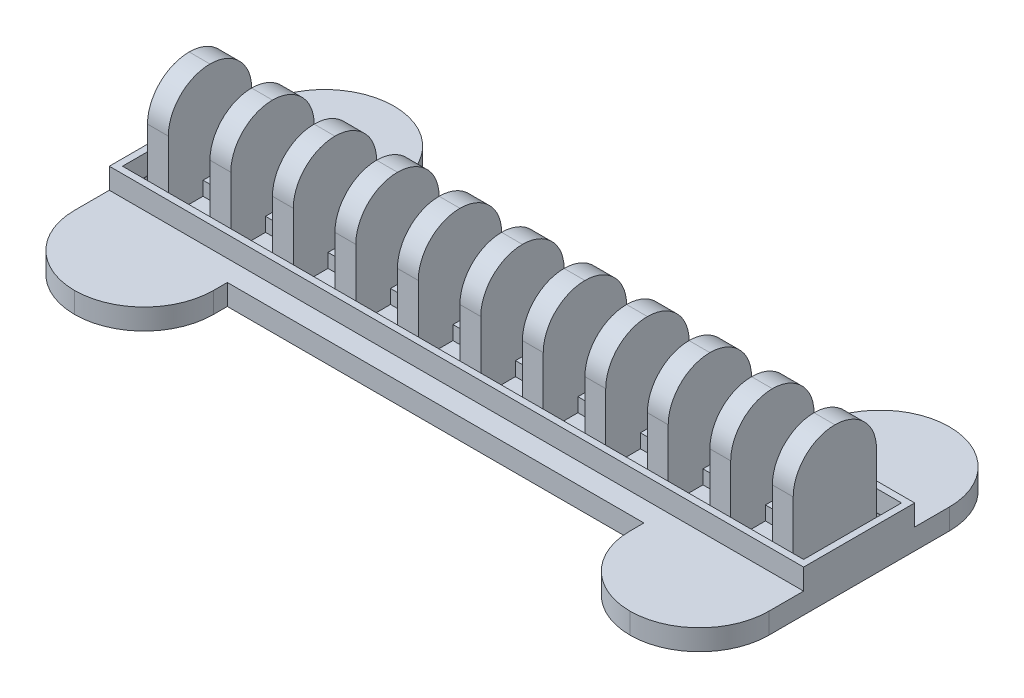
SolidWorks part; units mm, degrees
ref_plane "Front Plane" through (0, 0, 0) normal (0, 0, 1) x (1, 0, 0)
ref_plane "Top Plane" through (0, 0, 0) normal (0, 1, 0) x (1, 0, 0)
ref_plane "Right Plane" through (0, 0, 0) normal (1, 0, 0) x (0, 0, -1)
sketch "Sketch1" plane through (0, 0, 0) normal (0, 1, 0) x (1, 0, 0)
  line L1 (0, 0) -> (100, 0)
  line L2 (0, 0) -> (0, 16)
  line L3 (0, 16) -> (100, 16)
  line L4 (100, 0) -> (100, 16)
  dimension "D1" = 16
  dimension "D2" = 100
extrude "Boss-Extrude1" add sketch "Sketch1" along normal blind 3
sketch "Sketch2" plane through (0, 3, 0) normal (0, 1, 0) x (1, 0, 0)
  line L0 (0, 16) -> (0, 0) construction
  line L1 (1, 1) -> (99, 1)
  line L2 (1, 1) -> (1, 15)
  line L3 (1, 15) -> (99, 15)
  line L4 (99, 1) -> (99, 15)
  line L5 (100, 16) -> (0, 16) construction
  line L6 (0, 0) -> (100, 0) construction
  line L7 (100, 0) -> (100, 16) construction
  dimension "D1" = 1
  dimension "D2" = 1
  dimension "D3" = 1
  dimension "D4" = 1
extrude "Cut-Extrude1" cut sketch "Sketch2" against normal blind 1
sketch "Sketch5" plane through (0, 0, 0) normal (0, 0, 1) x (1, 0, 0)
  line L0 (0, 0) -> (100, 0) construction
  line L1 (0, 3) -> (20, 3)
  line L2 (0, 3) -> (0, 0)
  line L3 (0, 0) -> (20, 0)
  line L4 (20, 3) -> (20, 0)
  line L6 (100, 3) -> (80, 3)
  line L7 (100, 3) -> (100, 0)
  line L8 (100, 0) -> (80, 0)
  line L9 (80, 3) -> (80, 0)
  dimension "D1" = 20
  dimension "D2" = 20
extrude "Boss-Extrude4" add sketch "Sketch5" along normal blind 15
sketch "Sketch6" plane through (0, 0, -16) normal (0, 0, -1) x (-1, 0, 0)
  line L0 (-100, 0) -> (0, 0) construction
  line L1 (-100, 3) -> (-80, 3)
  line L2 (-100, 3) -> (-100, 0)
  line L3 (-100, 0) -> (-80, 0)
  line L4 (-80, 3) -> (-80, 0)
  line L6 (0, 3) -> (-20, 3)
  line L7 (0, 3) -> (0, 0)
  line L8 (0, 0) -> (-20, 0)
  line L9 (-20, 3) -> (-20, 0)
  dimension "D1" = 20
  dimension "D2" = 20
extrude "Boss-Extrude5" add sketch "Sketch6" along normal blind 15
fillet "Fillet18" radius 10 8 edges at (20, 1.5, 15) (0, 1.5, 15) (80, 1.5, 15) (100, 1.5, 15) (0, 1.5, -31) (20, 1.5, -31) (80, 1.5, -31) (100, 1.5, -31)
sketch "Sketch7" plane through (0, 2, 0) normal (0, 1, 0) x (1, 0, 0)
  line L0 (99, 1) -> (99, 15) construction
  line L1 (96.5, 2) -> (93.5, 2)
  line L2 (96.5, 2) -> (96.5, 14)
  line L3 (96.5, 14) -> (93.5, 14)
  line L4 (93.5, 2) -> (93.5, 14)
  line L5 (1, 1) -> (99, 1) construction
  line L6 (87.5, 2) -> (87.5, 14)
  line L7 (87.5, 2) -> (84.5, 2)
  line L8 (84.5, 2) -> (84.5, 14)
  line L9 (87.5, 14) -> (84.5, 14)
  line L10 (78.5, 2) -> (78.5, 14)
  line L11 (78.5, 2) -> (75.5, 2)
  line L12 (75.5, 2) -> (75.5, 14)
  line L13 (78.5, 14) -> (75.5, 14)
  line L14 (69.5, 2) -> (69.5, 14)
  line L15 (69.5, 2) -> (66.5, 2)
  line L16 (66.5, 2) -> (66.5, 14)
  line L17 (69.5, 14) -> (66.5, 14)
  line L18 (60.5, 2) -> (60.5, 14)
  line L19 (60.5, 2) -> (57.5, 2)
  line L20 (57.5, 2) -> (57.5, 14)
  line L21 (60.5, 14) -> (57.5, 14)
  line L22 (51.5, 2) -> (51.5, 14)
  line L23 (51.5, 2) -> (48.5, 2)
  line L24 (48.5, 2) -> (48.5, 14)
  line L25 (51.5, 14) -> (48.5, 14)
  line L26 (42.5, 2) -> (42.5, 14)
  line L27 (42.5, 2) -> (39.5, 2)
  line L28 (39.5, 2) -> (39.5, 14)
  line L29 (42.5, 14) -> (39.5, 14)
  line L30 (33.5, 2) -> (33.5, 14)
  line L31 (33.5, 2) -> (30.5, 2)
  line L32 (30.5, 2) -> (30.5, 14)
  line L33 (33.5, 14) -> (30.5, 14)
  line L34 (24.5, 2) -> (24.5, 14)
  line L35 (24.5, 2) -> (21.5, 2)
  line L36 (21.5, 2) -> (21.5, 14)
  line L37 (24.5, 14) -> (21.5, 14)
  line L38 (15.5, 2) -> (15.5, 14)
  line L39 (15.5, 2) -> (12.5, 2)
  line L40 (12.5, 2) -> (12.5, 14)
  line L41 (15.5, 14) -> (12.5, 14)
  line L42 (6.5, 2) -> (6.5, 14)
  line L43 (6.5, 2) -> (3.5, 2)
  line L44 (3.5, 2) -> (3.5, 14)
  line L45 (6.5, 14) -> (3.5, 14)
  line L46 (96.5, 2) -> (87.5, 2) construction
  dimension "D1" = 12
  dimension "D2" = 3
  dimension "D3" = 2.5
  dimension "D4" = 1
  dimension "D6" = 9
  dimension "D5" = 11
extrude "Boss-Extrude6" add sketch "Sketch7" along normal blind 16
sketch "Sketch8" plane through (0, 2, 0) normal (0, 1, 0) x (1, 0, 0)
  line L0 (93.5, 14) -> (93.5, 2) construction
  line L1 (93.5, 7) -> (87.5, 7)
  line L2 (93.5, 7) -> (93.5, 9)
  line L3 (93.5, 9) -> (87.5, 9)
  line L4 (87.5, 7) -> (87.5, 9)
  line L5 (87.5, 2) -> (87.5, 14) construction
  line L6 (99, 15) -> (1, 15) construction
  line L8 (84.5, 7) -> (84.5, 9)
  line L9 (84.5, 7) -> (78.5, 7)
  line L10 (78.5, 7) -> (78.5, 9)
  line L11 (84.5, 9) -> (78.5, 9)
  line L12 (75.5, 7) -> (75.5, 9)
  line L13 (75.5, 7) -> (69.5, 7)
  line L14 (69.5, 7) -> (69.5, 9)
  line L15 (75.5, 9) -> (69.5, 9)
  line L16 (66.5, 7) -> (66.5, 9)
  line L17 (66.5, 7) -> (60.5, 7)
  line L18 (60.5, 7) -> (60.5, 9)
  line L19 (66.5, 9) -> (60.5, 9)
  line L20 (57.5, 7) -> (57.5, 9)
  line L21 (57.5, 7) -> (51.5, 7)
  line L22 (51.5, 7) -> (51.5, 9)
  line L23 (57.5, 9) -> (51.5, 9)
  line L24 (48.5, 7) -> (48.5, 9)
  line L25 (48.5, 7) -> (42.5, 7)
  line L26 (42.5, 7) -> (42.5, 9)
  line L27 (48.5, 9) -> (42.5, 9)
  line L28 (39.5, 7) -> (39.5, 9)
  line L29 (39.5, 7) -> (33.5, 7)
  line L30 (33.5, 7) -> (33.5, 9)
  line L31 (39.5, 9) -> (33.5, 9)
  line L32 (30.5, 7) -> (30.5, 9)
  line L33 (30.5, 7) -> (24.5, 7)
  line L34 (24.5, 7) -> (24.5, 9)
  line L35 (30.5, 9) -> (24.5, 9)
  line L36 (21.5, 7) -> (21.5, 9)
  line L37 (21.5, 7) -> (15.5, 7)
  line L38 (15.5, 7) -> (15.5, 9)
  line L39 (21.5, 9) -> (15.5, 9)
  line L40 (12.5, 7) -> (12.5, 9)
  line L41 (12.5, 7) -> (6.5, 7)
  line L42 (6.5, 7) -> (6.5, 9)
  line L43 (12.5, 9) -> (6.5, 9)
  line L44 (93.5, 7) -> (84.5, 7) construction
  dimension "D1" = 2
  dimension "D2" = 6
  dimension "D3" = 10
  dimension "D4" = 9
extrude "Boss-Extrude7" add sketch "Sketch8" along normal blind 2
fillet "Fillet19" radius 6 22 edges at (95, 18, -2) (95, 18, -14) (86, 18, -2) (86, 18, -14) (77, 18, -2) (77, 18, -14) (68, 18, -2) (68, 18, -14) (59, 18, -2) (59, 18, -14) (50, 18, -2) (50, 18, -14) (41, 18, -2) (41, 18, -14) (32, 18, -2) (32, 18, -14) (23, 18, -14) (23, 18, -2) (14, 18, -2) (14, 18, -14) (5, 18, -2) (5, 18, -14)
sketch "Sketch10" plane through (0, 0, -16) normal (0, 0, -1) x (-1, 0, 0)
  line L1 (-80, 3) -> (-20, 3)
  line L2 (-80, 3) -> (-80, 0)
  line L3 (-80, 0) -> (-20, 0)
  line L4 (-20, 3) -> (-20, 0)
extrude "Boss-Extrude8" add sketch "Sketch10" along normal blind 3
sketch "Sketch11" plane through (0, 0, 0) normal (0, 0, 1) x (1, 0, 0)
  line L1 (20, 3) -> (80, 3)
  line L2 (20, 3) -> (20, 0)
  line L3 (20, 0) -> (80, 0)
  line L4 (80, 3) -> (80, 0)
extrude "Boss-Extrude9" add sketch "Sketch11" along normal blind 3
sketch "Sketch12" plane through (0, 3, 0) normal (0, 1, 0) x (1, 0, 0)
  line L0 (100, -5) -> (100, 21) construction
  line L1 (100, 14.9979) -> (99.05, 14.9979)
  line L2 (100, 14.9979) -> (100, 0.9979)
  line L3 (100, 0.9979) -> (99.05, 0.9979)
  line L4 (99.05, 14.9979) -> (99.05, 0.9979)
  line L5 (0, 21) -> (0, -5) construction
  line L6 (0, 14.9979) -> (0.95, 14.9979)
  line L7 (0, 14.9979) -> (0, 0.9979)
  line L8 (0, 0.9979) -> (0.95, 0.9979)
  line L9 (0.95, 14.9979) -> (0.95, 0.9979)
  dimension "D1" = 0.95
  dimension "D2" = 14
  dimension "D3" = 0.95
  dimension "D4" = 14
extrude "Boss-Extrude10" add sketch "Sketch12" along normal blind 3
sketch "Sketch13" plane through (0, 3, 0) normal (0, 1, 0) x (1, 0, 0)
  line L0 (0, 21) -> (0, 14.9979) construction
  line L1 (0, 15.05) -> (100, 15.05)
  line L2 (0, 15.05) -> (0, 16)
  line L3 (0, 16) -> (100, 16)
  line L4 (100, 15.05) -> (100, 16)
  line L5 (100, 14.9979) -> (100, 21) construction
  line L6 (100, -5) -> (100, 0.9979) construction
  line L7 (0, 0) -> (100, 0)
  line L8 (0, 0) -> (0, 0.95)
  line L9 (0, 0.95) -> (100, 0.95)
  line L10 (100, 0) -> (100, 0.95)
  line L11 (99, 15) -> (1, 15) construction
  line L13 (1, 1) -> (99, 1) construction
  dimension "D1" = 0.95
  dimension "D2" = 0.05
  dimension "D3" = 0.05
extrude "Boss-Extrude11" add sketch "Sketch13" along normal blind 3
sketch "Sketch14" plane through (0, 3, 0) normal (0, 1, 0) x (1, 0, 0)
  line L0 (0.95, 14.9979) -> (0, 14.9979) construction
  line L1 (0, 15.05) -> (0.95, 15.05)
  line L2 (0, 15.05) -> (0, 14.9979)
  line L3 (0, 14.9979) -> (0.95, 14.9979)
  line L4 (0.95, 15.05) -> (0.95, 14.9979)
  line L5 (0.95, 14.9979) -> (0, 14.9979) construction
extrude "Boss-Extrude12" add sketch "Sketch14" along normal blind 3
sketch "Sketch15" plane through (0, 3, 0) normal (0, 1, 0) x (1, 0, 0)
  line L0 (100, 0.95) -> (0, 0.95) construction
  line L1 (0, 0.9979) -> (0.95, 0.9979)
  line L2 (0, 0.9979) -> (0, 0.95)
  line L3 (0, 0.95) -> (0.95, 0.95)
  line L4 (0.95, 0.9979) -> (0.95, 0.95)
  line L6 (100, 0.9979) -> (99.0503, 0.9979)
  line L7 (100, 0.9979) -> (100, 0.95)
  line L8 (100, 0.95) -> (99.0503, 0.95)
  line L9 (99.0503, 0.9979) -> (99.0503, 0.95)
  line L10 (100, 15.05) -> (99.05, 15.05)
  line L11 (100, 15.05) -> (100, 14.9979)
  line L12 (100, 14.9979) -> (99.05, 14.9979)
  line L13 (99.05, 15.05) -> (99.05, 14.9979)
extrude "Boss-Extrude13" add sketch "Sketch15" along normal blind 3
ref_plane "Plane1" through (0, 6, 0) normal (0, 0, 1) x (1, 0, 0)
